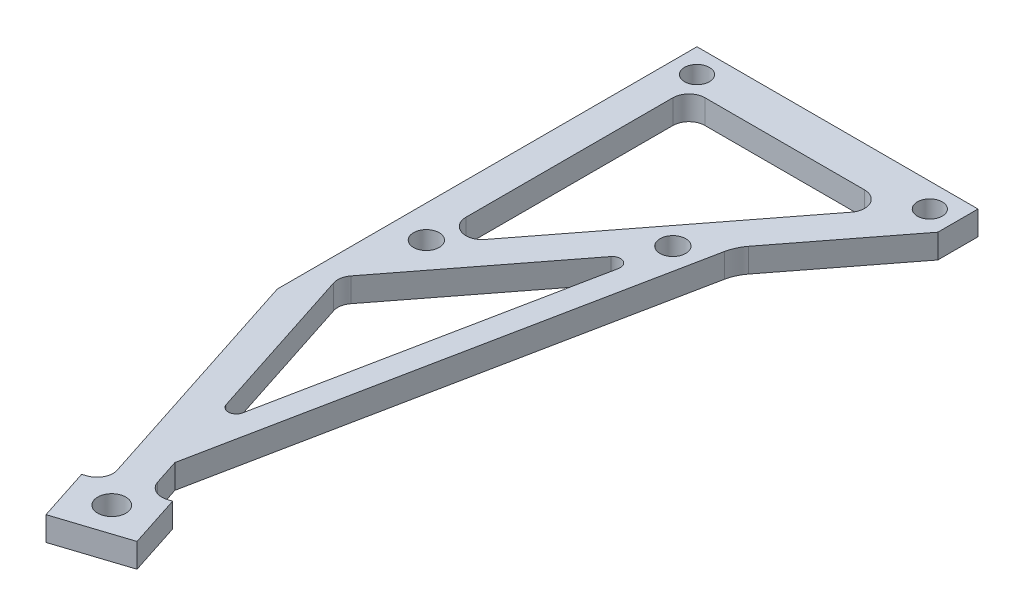
SolidWorks part; units mm, degrees
material "Thornel Mat VMA"
ref_plane "Front" through (0, 0, 0) normal (0, 0, 1) x (1, 0, 0)
ref_plane "Top" through (0, 0, 0) normal (0, 1, 0) x (1, 0, 0)
ref_plane "Right" through (0, 0, 0) normal (1, 0, 0) x (0, 0, -1)
sketch "草图8" plane through (0, 0, 0) normal (0, 1, 0) x (1, 0, 0)
  line L3 (0, 0) -> (83.6, 0) construction
  line L4 (83.6, 0) -> (83.6, -28.36) construction
  line L5 (83.6, -28.36) -> (28, -85.8808)
  dimension "D1" = 28
  dimension "D5" = 83.6
  dimension "D6" = 28.36
  dimension "D7" = 80
sketch "草图1" plane through (0, 0, 0) normal (0, 0, 1) x (1, 0, 0)
  line L0 (26.315, 0) -> (-26.315, 0) construction
  line L1 (50, -7) -> (-50, -7)
  line L2 (50, -7) -> (50, 7)
  line L3 (50, 7) -> (-50, 7)
  line L4 (-50, -7) -> (-50, 7)
  line L5 (50, -7) -> (-50, 7) construction
  line L6 (50, 7) -> (-50, -7) construction
  line L7 (-26.315, -2.5) -> (-26.315, 2.5) construction
  line L8 (26.315, -2.5) -> (26.315, 2.5) construction
  circle A0 centre (-26.315, 2.5) radius 1.75
  circle A1 centre (-26.315, -2.5) radius 1.75
  circle A2 centre (26.315, -2.5) radius 1.75
  circle A3 centre (26.315, 2.5) radius 1.75
  point P0 (0, 0)
  point P9 (0, 0)
  point P12 (-26.315, 0)
  point P15 (26.315, 0)
  dimension "D3" = 3.5
  dimension "D4" = 14
  dimension "D1" = 52.63
  dimension "D2" = 5
  dimension "D5" = 100
  dimension "D6" = 5
extrude "凸台-拉伸1" add sketch "草图1" against normal blind 3 and the other way blind 4 contours A2 | A1 | L4 L1 L2 L3 A3 A2 A1 A0
ref_plane "基准面1" through (15, 0, 0) normal (1, 0, 0) x (0, 0, -1)
sketch "草图2" plane through (15, 0, 0) normal (1, 0, 0) x (0, 0, -1)
  line L0 (-3, 7) -> (-91, 7)
  line L1 (-91, 7) -> (-91, -7)
  line L2 (-91, -7) -> (-3, -7)
  line L3 (-3, -7) -> (-3, 7)
  point P7 (-91, 0)
  dimension "D1" = 88
  dimension "D2" = 14
extrude "凸台-拉伸2" add sketch "草图2" along normal blind 3
sketch "草图10" plane through (18, 0, 0) normal (1, 0, 0) x (0, 0, -1)
  line L0 (-91, -3) -> (-91, -7)
  line L1 (-91, 7) -> (-91, -7) construction
  line L2 (-91, -7) -> (-3, -7)
  line L3 (-3, -7) -> (-3, -3)
  line L5 (-3, -3) -> (-91, -3)
  line L6 (-91, 7) -> (-91, 3)
  line L7 (-91, 3) -> (-3, 3)
  line L8 (-3, 3) -> (-3, 7)
  line L9 (-3, 7) -> (-91, 7)
  dimension "D1" = 4
  dimension "D2" = 4
extrude "凸台-拉伸5" add sketch "草图10" along normal blind 35
sketch "草图11" plane through (0, 0, 0) normal (0, 1, 0) x (1, 0, 0)
  line L1 (27.3377, -77.3537) -> (28.9833, -82.429)
  line L4 (28, -85.8808) -> (29.2098, -89.612) construction
  line L5 (22.8002, -84.4339) -> (25.1783, -83.6628)
  line L6 (25.1783, -83.6628) -> (15, -52.2717)
  line L7 (18.5523, -45.7666) -> (17.5268, -47.096)
  line L8 (17.5268, -47.096) -> (25.4488, -71.5283)
  line L10 (15, -52.2717) -> (15, -43.7357)
  line L11 (25.4488, -71.5283) -> (34.8853, -24.5937)
  line L13 (53, -91) -> (15, -91) construction
  line L15 (24.9292, -91) -> (22.8002, -84.4339)
  line L16 (15, -50) -> (15, 50) construction
  line L17 (15, -43.7357) -> (15, -91)
  line L18 (15, -91) -> (24.9292, -91)
  line L20 (18.5523, -45.7666) -> (34.8853, -24.5937)
  line L21 (19, -32.7703) -> (19, -5)
  line L22 (28.9833, -82.429) -> (31.3614, -81.658)
  line L23 (19, -5) -> (44.9482, -5)
  line L24 (44.9482, -5) -> (22.5836, -33.9919)
  line L25 (27.3377, -77.3537) -> (39.024, -19.2285)
  line L27 (24.9292, -91) -> (33.4904, -88.2241)
  line L28 (24.9292, -91) -> (53, -91)
  line L29 (33.4904, -88.2241) -> (31.3614, -81.658)
  line L31 (27.3377, -77.3537) -> (25.4488, -71.5283) construction
  line L32 (39.024, -19.2285) -> (50, -5)
  line L33 (53, -91) -> (53, 0)
  line L34 (0, 0) -> (83.6, 0) construction
  line L35 (53, 0) -> (50, 0)
  line L36 (50, 0) -> (50, -5)
  line L37 (50, -3) -> (50, 3) construction
  circle A0 centre (19, -37.7023) radius 1.6
  arc A1 (19, -32.7703) -> (22.5836, -33.9919) centre (21, -32.7703) ccw
  dimension "D4" = 3.2
  dimension "D8" = 2
  dimension "D1" = 4
  dimension "D2" = 9
  dimension "D3" = 4
  dimension "D5" = 2.5
  dimension "D6" = 2.5
  dimension "D7" = 3
  dimension "D9" = 5
  dimension "D10" = 33
extrude "切除-拉伸3" cut sketch "草图11" against normal mid plane 50
sketch "草图19" plane through (0, 0, 4) normal (0, 0, 1) x (1, 0, 0)
  line L1 (-50, 7) -> (15, 7)
  line L2 (-50, 7) -> (-50, -7)
  line L3 (-50, -7) -> (15, -7)
  line L4 (15, 7) -> (15, -7)
extrude "切除-拉伸7" cut sketch "草图19" against normal blind 10
sketch "草图20" plane through (15, 0, 0) normal (-1, 0, 0) x (0, 0, 1)
  line L2 (0, 4) -> (0, -4)
  line L5 (-3, 7) -> (52.2717, 7) construction
  line L6 (0, 4) -> (17.6341, 3)
  line L7 (91, 3) -> (84.4339, 3) construction
  line L8 (17.6341, 3) -> (17.6341, -3)
  line L9 (84.4339, -3) -> (91, -3) construction
  line L10 (17.6341, -3) -> (0, -4)
  point P7 (0, 0)
  dimension "D1" = 3
sketch "草图21" plane through (0, 0, 0.2854) normal (0, -1, 0) x (1, 0, 0)
  circle A0 centre (28, 85.5954) radius 1.75
  dimension "D1" = 3.5
extrude "切除-拉伸9" cut sketch "草图21" against normal mid plane 50
mirror "镜向1" [suppressed] about plane through (0, 0, 0) normal (1, 0, 0)
fillet "圆角3" radius 2 9 edges at (25.1783, 5, 83.6628) (25.1783, -5, 83.6628) (17.5268, 0, 47.096) (44.9482, -5, 5) (44.9482, 5, 5) (19, 5, 5) (19, -5, 5) (28.9833, 5, 82.429) (28.9833, -5, 82.429)
fillet "圆角4" radius 1 4 edges at (25.4488, 5, 71.5283) (25.4488, -5, 71.5283) (34.8853, 5, 24.5937) (34.8853, -5, 24.5937)
fillet "圆角5" radius 5 2 edges at (39.024, 5, 19.2285) (39.024, -5, 19.2285)
sketch "草图27" plane through (0, 7, 0) normal (0, 1, 0) x (1, 0, 0)
  line L0 (15, -50) -> (15, 50) construction
  line L1 (50, 0) -> (15, 0)
  line L2 (50, 0) -> (50, 3)
  line L3 (50, 3) -> (15, 3)
  line L4 (15, 0) -> (15, 3)
  line L8 (50, 0) -> (15, 0)
  line L11 (15, 0) -> (15, -3)
  line L12 (0, 0) -> (83.6, 0) construction
  line L13 (50, -5) -> (50, 3) construction
  line M7 (15, 3) -> (15, -52.2717)
  line M18 (50, -5) -> (50, 3)
  line M33 (50, 3) -> (15, 3)
extrude "切除-拉伸14" cut sketch "草图27" against normal up to next contours L1 M18 M33 M7
sketch "草图28" plane through (0, 7, 0) normal (0, 1, 0) x (1, 0, 0)
  line L1 (56.2492, -101.3031) -> (0, -101.3031)
  line L2 (56.2492, -101.3031) -> (56.2492, 7.799)
  line L3 (56.2492, 7.799) -> (0, 7.799)
  line L4 (0, -101.3031) -> (0, 7.799)
extrude "切除-拉伸15" cut sketch "草图28" against normal up to surface (10 mm away) up to face at (28, -3, 84.1308)
sketch "草图33" plane through (0, -7, 0) normal (0, -1, 0) x (1, 0, 0)
  line L12 (15, 52.2717) -> (15, 0)
  line L13 (15, 0) -> (50, 0)
  line L14 (50, 0) -> (50, 5)
  line L15 (50, 5) -> (39.7369, 18.3044)
  line L16 (38.7939, 20.3728) -> (27.3377, 77.3537)
  line L17 (27.3377, 77.3537) -> (28.3664, 80.5266)
  line L18 (30.8858, 81.8122) -> (31.3614, 81.658)
  line L19 (31.3614, 81.658) -> (33.4904, 88.2241)
  line L20 (33.4904, 88.2241) -> (24.9292, 91)
  line L21 (24.9292, 91) -> (22.8002, 84.4339)
  line L22 (22.8002, 84.4339) -> (23.2758, 84.2796)
  line L23 (24.5615, 81.7603) -> (15, 52.2717)
  line L24 (15, 52.2717) -> (15, 0)
  line L25 (15, 0) -> (50, 0)
  line L26 (50, 0) -> (50, 5)
  line L27 (50, 5) -> (39.7369, 18.3044)
  line L28 (38.7939, 20.3728) -> (27.3377, 77.3537)
  line L29 (27.3377, 77.3537) -> (28.3664, 80.5266)
  line L30 (30.8858, 81.8122) -> (31.3614, 81.658)
  line L31 (31.3614, 81.658) -> (33.4904, 88.2241)
  line L32 (33.4904, 88.2241) -> (24.9292, 91)
  line L33 (24.9292, 91) -> (22.8002, 84.4339)
  line L34 (22.8002, 84.4339) -> (23.2758, 84.2796)
  line L35 (24.5615, 81.7603) -> (15, 52.2717)
  arc A3 (38.7939, 20.3728) -> (39.7369, 18.3044) centre (43.6958, 21.3583) ccw
  arc A4 (30.8858, 81.8122) -> (28.3664, 80.5266) centre (30.2689, 79.9097) ccw
  arc A5 (24.5615, 81.7603) -> (23.2758, 84.2796) centre (22.659, 82.3772) ccw
  arc A6 (38.7939, 20.3728) -> (39.7369, 18.3044) centre (43.6958, 21.3583) ccw
  arc A7 (30.8858, 81.8122) -> (28.3664, 80.5266) centre (30.2689, 79.9097) ccw
  arc A8 (24.5615, 81.7603) -> (23.2758, 84.2796) centre (22.659, 82.3772) ccw
  dimension "D1" = 0
extrude "切除-拉伸16" cut sketch "草图33" against normal blind 1
hole_wizard "M2 间隙孔1" [suppressed] positions "3D草图4" profile "草图32" hole size "M2" standard "GB"
sketch3d "3D草图4"
  line L4 (50, -4, 0) -> (15, -4, 0) construction
  line L7 (50, -3, 3) -> (50, -3, 0) construction
  line L8 (15, -3, 0) -> (15, -3, 52.2717) construction
  point P0 (47.5, -3, 2.2913)
  point P2 (17.5, -3, 2.2913)
  dimension "D1" = 2.5
  dimension "D2" = 2.5
  dimension "D3" = 2.5
  dimension "D4" = 2.5
sketch "草图32" plane through (47.5, -3, 2.2913) normal (1, 0, 0) x (0, 0, 1)
  line L0 (0, 0) -> (0, 3)
  line L1 (0, 3) -> (1.2, 3)
  line L2 (1.2, 3) -> (1.2, 0)
  line L5 (1.2, 0) -> (0, 0)
  line L11 (0, -6.35) -> (0, 107.95) construction
  dimension "通孔孔直径" = 2.4
  dimension "通孔孔深度" = 3
sketch "草图34" plane through (0, -3, 0) normal (0, 1, 0) x (1, 0, 0)
  line L0 (0, 0) -> (83.6, 0) construction
  line L1 (15, -17.6341) -> (15, 0) construction
  line L3 (50, 0) -> (50, -5) construction
  circle A0 centre (18, -3) radius 1.55
  circle A1 centre (47, -3) radius 1.55
  point P12 (50, -2.5)
  dimension "D1" = 3.1
  dimension "D2" = 3.1
  dimension "D3" = 3
  dimension "D4" = 3
  dimension "D5" = 3
  dimension "D6" = 3
extrude "切除-拉伸17" cut sketch "草图34" against normal through all
sketch "草图35" plane through (0, -3, 0) normal (0, 1, 0) x (1, 0, 0)
  line L0 (50, -5) -> (50, 0) construction
  line L1 (0, 0) -> (83.6, 0) construction
  circle A0 centre (35, -23) radius 1.6
  dimension "D2" = 3.2
  dimension "D1" = 15
  dimension "D3" = 23
extrude "切除-拉伸18" cut sketch "草图35" against normal blind 10
